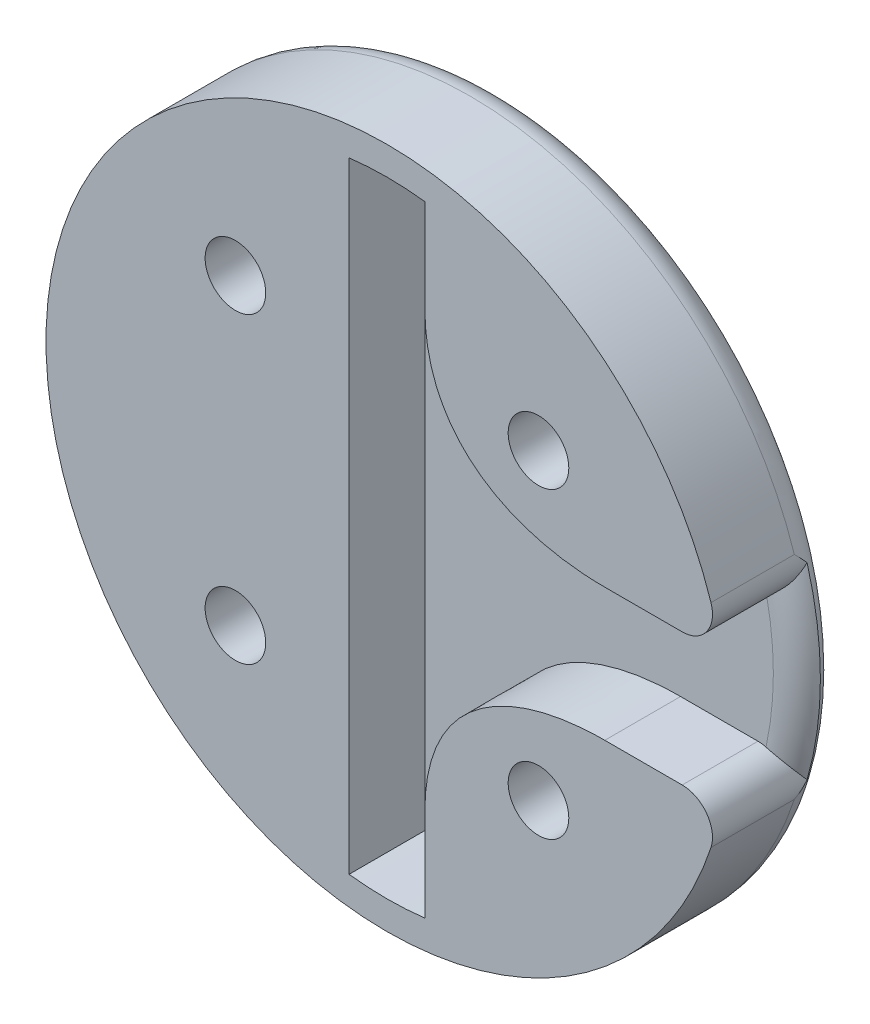
SolidWorks part; units mm, degrees
ref_plane "Front Plane" through (0, 0, 0) normal (1, 0, 0) x (0, 1, 0)
ref_plane "Top Plane" through (0, 0, 0) normal (0, 0, 1) x (0, 1, 0)
ref_plane "Right Plane" through (0, 0, 0) normal (0, 1, 0) x (-1, 0, 0)
sketch "Sketch1" plane through (0, 0, 0) normal (0, 0, 1) x (0, 1, 0)
  circle A0 centre (0, 0) radius 18
  dimension "D1" = 36
extrude "Boss-Extrude1" add sketch "Sketch1" along normal blind 6
sketch "Sketch2" plane through (0, 0, 6) normal (0, 0, 1) x (1, 0, 0)
  line L0 (11.5, 3.5) -> (17.6564, 3.5)
  line L1 (-11.5, -11.5) -> (11.5, -11.5) construction
  line L2 (-11.5, -11.5) -> (-11.5, 11.5) construction
  line L3 (-11.5, 11.5) -> (11.5, 11.5) construction
  line L4 (11.5, -11.5) -> (11.5, 11.5) construction
  line L5 (-11.5, -11.5) -> (11.5, 11.5) construction
  line L6 (-11.5, 11.5) -> (11.5, -11.5) construction
  line L7 (11.5, -3.5) -> (17.6564, -3.5)
  line L8 (-2, 16.3783) -> (-2, -16.3783)
  line L9 (2, 14.5) -> (2, -16.3783) construction
  line L10 (0, 0) -> (31.1189, 0) construction
  line L11 (2, 11.5) -> (2, 16.3783)
  line L12 (2, 16.3783) -> (2, 11.5)
  line L13 (2, -16.3783) -> (2, -11.5)
  circle A0 centre (8, 8) radius 1.6
  circle A1 centre (8, -8) radius 1.6
  circle A2 centre (-8, -8) radius 1.6
  circle A3 centre (-8, 8) radius 1.6
  circle A4 centre (0, 0) radius 18 construction
  arc A5 (17.6564, 3.5) -> (17.6564, -3.5) centre (0, 0) cw
  circle A6 centre (0, 0) radius 16.5 construction
  circle A7 centre (0, 14.5) radius 2 construction
  arc A8 (-2, 16.3783) -> (2, 16.3783) centre (0, 0) cw
  arc A9 (6, 16.3783) -> (2, 16.3783) centre (4, 0) ccw
  arc A10 (6, 16.3783) -> (2, 16.3783) centre (4, 0) ccw
  arc A11 (-2, -16.3783) -> (2, -16.3783) centre (0, 0) ccw
  spline S0 degree 3 poles (2, 11.5) (2, 5.6804) (6.7268, 3.5) (11.5, 3.5) knots 0 0 0 0 1 1 1 1
  spline S1 degree 3 poles (2, -11.5) (2, -5.6804) (6.7268, -3.5) (11.5, -3.5) knots 0 0 0 0 1 1 1 1
  point P0 (0, 0)
  circle M1 centre (0, 0) radius 18
  dimension "D1" = 23
  dimension "D2" = 3.2
  dimension "D5" = 7
  dimension "D6" = 1.5
  dimension "D7" = 4
  dimension "D4" = 16
  dimension "D8" = 4
  dimension "D9" = 4
  dimension "D3" = 4
extrude "Cut-Extrude1" cut sketch "Sketch2" against normal blind 4 contours L13 S1 L7 L0 S0 L11 A8 L8 A11 M1 region at (4.4959, 0, 6)
extrude "Cut-Extrude2" cut sketch "Sketch2<3>" against normal up to next contours A2 | A1 | A0 | A3 region at (8, 8, 6) region at (8, -8, 6) region at (-8, -8, 6) region at (-8, 8, 6)
sketch "Sketch2<3>" plane through (0, 0, 6) normal (0, 0, 1) x (1, 0, 0) same geometry as "Sketch2"
fillet "Fillet1" radius 1.6 4 edges at (18, 0, 2) (17.6564, -3.5, 4) (17.6564, 3.5, 4) (18, 0, 0)
chamfer "Chamfer1" distance 2.4 distance2 2.5 4 edges at (-6.4, -8, 0) (-6.4, 8, 0) (9.6, 8, 0) (9.6, -8, 0) first distance on face at (16.4, 0, 0)
